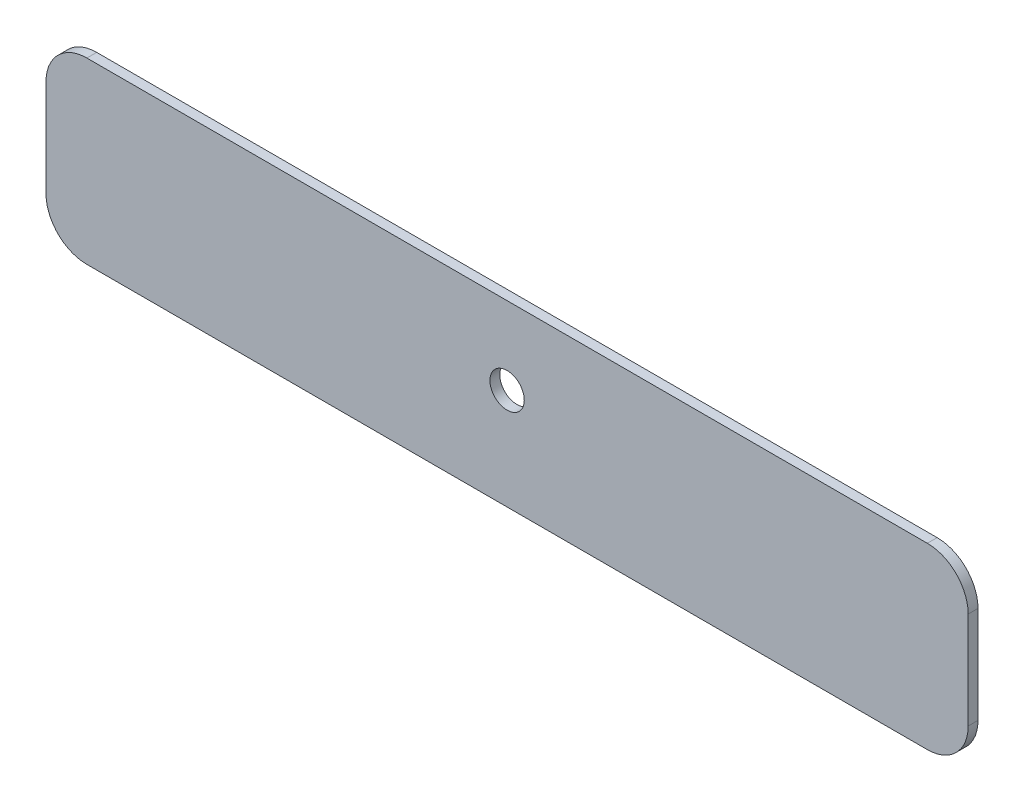
SolidWorks part; units mm, degrees
ref_plane "Front Plane" through (0, 0, 0) normal (0, 0, 1) x (1, 0, 0)
ref_plane "Top Plane" through (0, 0, 0) normal (0, 1, 0) x (1, 0, 0)
ref_plane "Right Plane" through (0, 0, 0) normal (1, 0, 0) x (0, 0, -1)
sketch "Sketch1" plane through (0, 0, 0) normal (0, 0, 1) x (1, 0, 0)
  line L2 (-56.4, 136.5) -> (-56.4, 114.6383)
  line L3 (-56.4, 114.6383) -> (56.4, 114.6383)
  line L4 (56.4, 136.5) -> (56.4, 114.6383)
  line L7 (0, 136.5) -> (-56.4, 136.5)
  line L8 (0, 136.5) -> (56.4, 136.5)
  line L11 (-56.4, 28.6363) -> (-56.4, 107.5) construction
  line L13 (56.4, 131.5) -> (56.4, 111.5) construction
  circle A0 centre (0, 127) radius 2.1 construction
  circle A1 centre (0, 127) radius 2.1
  point P3 (56.4, 136.5)
  dimension "D1" = 21.8617
  dimension "D2" = 112.8
  dimension "D3" = 4
extrude "Boss-Extrude1" add sketch "Sketch1" along normal blind 1.2
fillet "Fillet1" radius 5 4 edges at (56.4, 114.6383, 0.6) (-56.4, 114.6383, 0.6) (56.4, 136.5, 0.6) (-56.4, 136.5, 0.6)
